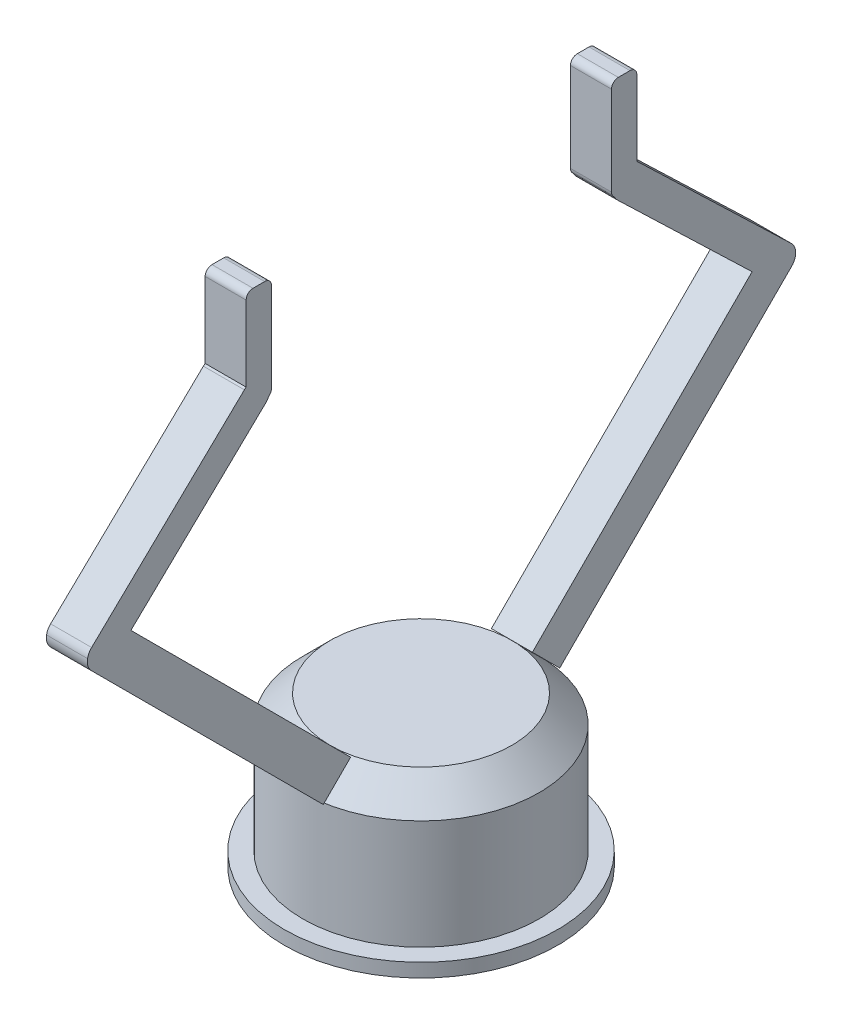
SolidWorks part; units mm, degrees
ref_plane "Front Plane" through (0, 0, 0) normal (0, 0, 1) x (1, 0, 0)
ref_plane "Top Plane" through (0, 0, 0) normal (0, 1, 0) x (1, 0, 0)
ref_plane "Right Plane" through (0, 0, 0) normal (1, 0, 0) x (0, 0, -1)
sketch "Sketch2" plane through (0, 0, 0) normal (0, 1, 0) x (1, 0, 0)
  circle A0 centre (0, 0) radius 100
  dimension "D1" = 200
extrude "Boss-Extrude1" add sketch "Sketch2" along normal blind 10
sketch "Sketch3" plane through (0, 10, 0) normal (0, 1, 0) x (1, 0, 0)
  circle A0 centre (0, 0) radius 86.4981
extrude "Boss-Extrude2" add sketch "Sketch3" along normal blind 100
chamfer "Chamfer1" distance 20 angle 45 1 edges at (0, 110, 86.4981)
sketch "Sketch4" plane through (0, 0, 0) normal (1, 0, 0) x (0, 0, -1)
  line L0 (-66.4981, 110) -> (-86.4981, 90)
  line L1 (-66.4981, 110) -> (-236.2038, 279.7056)
  line L2 (-86.4981, 90) -> (-256.2038, 259.7056)
  line L4 (-256.2038, 273.8478) -> (-250.3459, 279.7056)
  arc A1 (-256.2038, 259.7056) -> (-256.2038, 273.8478) centre (-249.1327, 266.7767) cw
  arc A2 (-236.2038, 279.7056) -> (-250.3459, 279.7056) centre (-243.2748, 272.6346) ccw
  point P8 (-263.2748, 266.7767)
  dimension "D2" = 10
  dimension "D1" = 250
extrude "Boss-Extrude3" add sketch "Sketch4" along normal blind 15 and the other way blind 15 separate body
sketch "Sketch5" plane through (0, 0, 0) normal (1, 0, 0) x (0, 0, -1)
  line L0 (-254.5947, 258.3581) -> (-256.2945, 260.1274)
  line L1 (-240.4555, 258.0747) -> (-128.6791, 365.4574)
  line L2 (-256.011, 274.2667) -> (-144.2347, 381.6495)
  line L3 (-128.3957, 379.5967) -> (-130.0954, 381.366)
  arc A0 (-128.6791, 365.4574) -> (-128.3957, 379.5967) centre (-135.607, 372.6688) ccw
  arc A1 (-144.2347, 381.6495) -> (-130.0954, 381.366) centre (-137.3068, 374.4381) cw
  arc A2 (-240.4555, 258.0747) -> (-254.5947, 258.3581) centre (-247.3834, 265.286) cw
  arc A3 (-256.2945, 260.1274) -> (-256.011, 274.2667) centre (-249.0831, 267.0553) cw
  point P8 (-137.0233, 388.5774)
  point P13 (-263.2224, 267.3388)
  dimension "D2" = 10
  dimension "D1" = 175
extrude "Boss-Extrude4" add sketch "Sketch5" along normal blind 15 and the other way blind 15
sketch "Sketch7" plane through (0, 0, 0) normal (1, 0, 0) x (0, 0, -1)
  line L0 (-129.3737, 367.6406) -> (-137.9217, 367.6406)
  line L1 (-124.3737, 372.6406) -> (-124.3737, 437.8516)
  line L2 (-142.9217, 372.6406) -> (-142.9217, 437.8516)
  line L3 (-129.3737, 442.8516) -> (-137.9217, 442.8516)
  arc A0 (-142.9217, 437.8516) -> (-137.9217, 442.8516) centre (-137.9217, 437.8516) cw
  arc A1 (-137.9217, 367.6406) -> (-142.9217, 372.6406) centre (-137.9217, 372.6406) cw
  arc A2 (-124.3737, 437.8516) -> (-129.3737, 442.8516) centre (-129.3737, 437.8516) ccw
  arc A3 (-124.3737, 372.6406) -> (-129.3737, 367.6406) centre (-129.3737, 372.6406) cw
  point P0 (-142.9217, 367.6406)
  dimension "D1" = 5
extrude "Boss-Extrude5" add sketch "Sketch7" along normal blind 15 and the other way blind 15
mirror "Mirror6" about plane through (0, 0, 0) normal (0, 0, 1) of bodies 105
